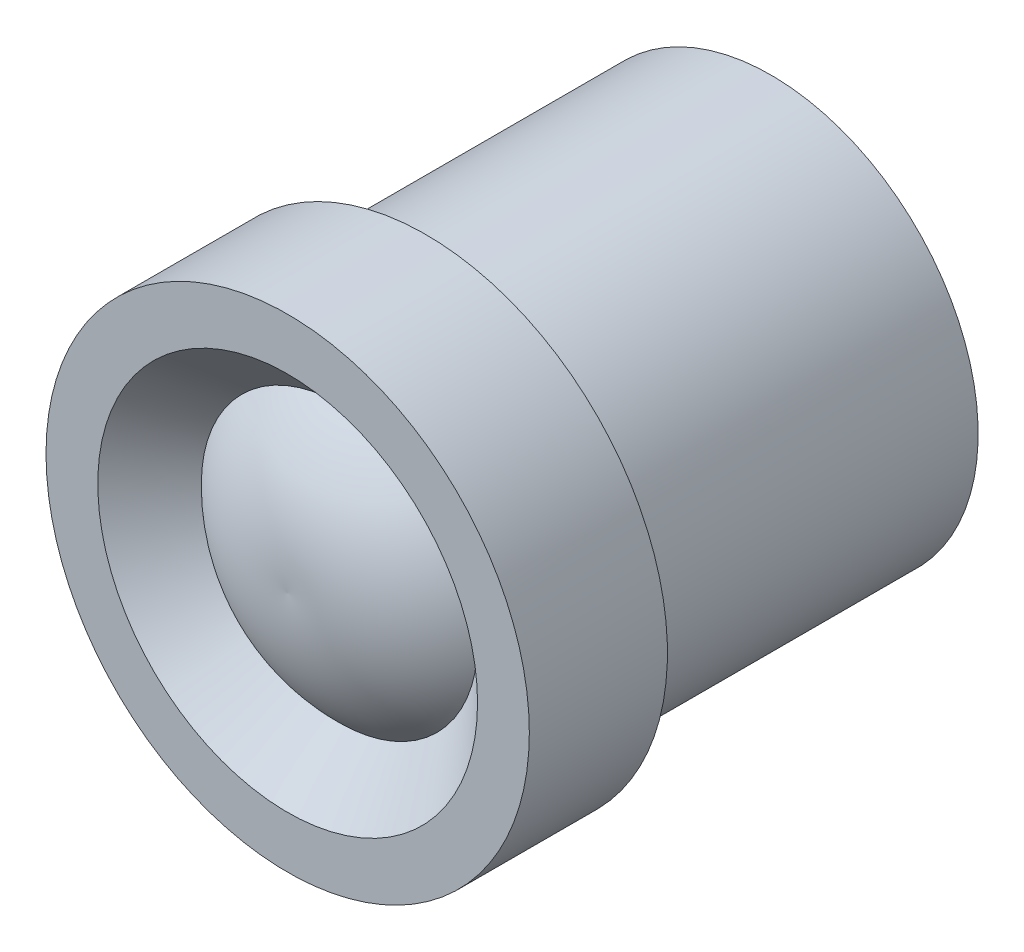
SolidWorks part; units mm, degrees
ref_plane "Front Plane" through (0, 0, 0) normal (0, 0, 1) x (1, 0, 0)
ref_plane "Top Plane" through (0, 0, 0) normal (0, 1, 0) x (1, 0, 0)
ref_plane "Right Plane" through (0, 0, 0) normal (1, 0, 0) x (0, 0, -1)
sketch "Sketch1" plane through (0, 0, 0) normal (0, 0, 1) x (1, 0, 0)
  circle A0 centre (0, 0) radius 7
  dimension "D1" = 14
extrude "Boss-Extrude1" add sketch "Sketch1" along normal blind 14 contours A0
sketch "Sketch2" plane through (0, 0, 0) normal (0, 0, -1) x (-1, 0, 0)
  circle A0 centre (0, 0) radius 6
  dimension "D1" = 12
extrude "Cut-Extrude1" cut sketch "Sketch2" against normal blind 10 flip side to cut
sketch "Sketch3" plane through (0, 0, 14) normal (0, 0, 1) x (1, 0, 0)
  circle A0 centre (0, 0) radius 5.5
  circle A1 centre (0, 0) radius 7 construction
  dimension "D1" = 1.5
extrude "Cut-Extrude2" cut sketch "Sketch3" against normal blind 1.5 draft 45
sketch "Sketch4" plane through (0, 0, 12.5) normal (0, 0, 1) x (1, 0, 0)
  circle A0 centre (0, 0) radius 4
  circle A1 centre (0, 0) radius 4 construction
extrude "Cut-Extrude3" cut sketch "Sketch4" against normal up to surface (12.5 mm away) up to face at (-6, 0, 0)
sketch "Sketch5" plane through (0, 0, 0) normal (0, 0, -1) x (-1, 0, 0)
  circle A0 centre (0, 0) radius 4
  circle A1 centre (0, 0) radius 4 construction
extrude "Boss-Extrude3" add sketch "Sketch5" against normal blind 12.5 separate body
sketch "Sketch6" plane through (0, 0, 0) normal (0, 1, 0) x (1, 0, 0)
  line L0 (-5.5, -14) -> (5.5, -14) construction
  line L1 (-4, -12.5) -> (4, -12.5) construction
  line L2 (4, -12.5) -> (-4, -12.5) construction
  line L3 (4, -12.5) -> (4, 0) construction
  line L4 (-4, -12.5) -> (0, -12.5)
  line L5 (0, -12.5) -> (0, -14)
  arc A0 (-4, -12.5) -> (0, -14) centre (-0.4126, -9.0171) ccw
  point P13 (0, -12.5)
  dimension "D1" = 5
revolve "Revolve1" add sketch "Sketch6" angle 360 about L5 region at (-1.5645, 0, 13.1355)
